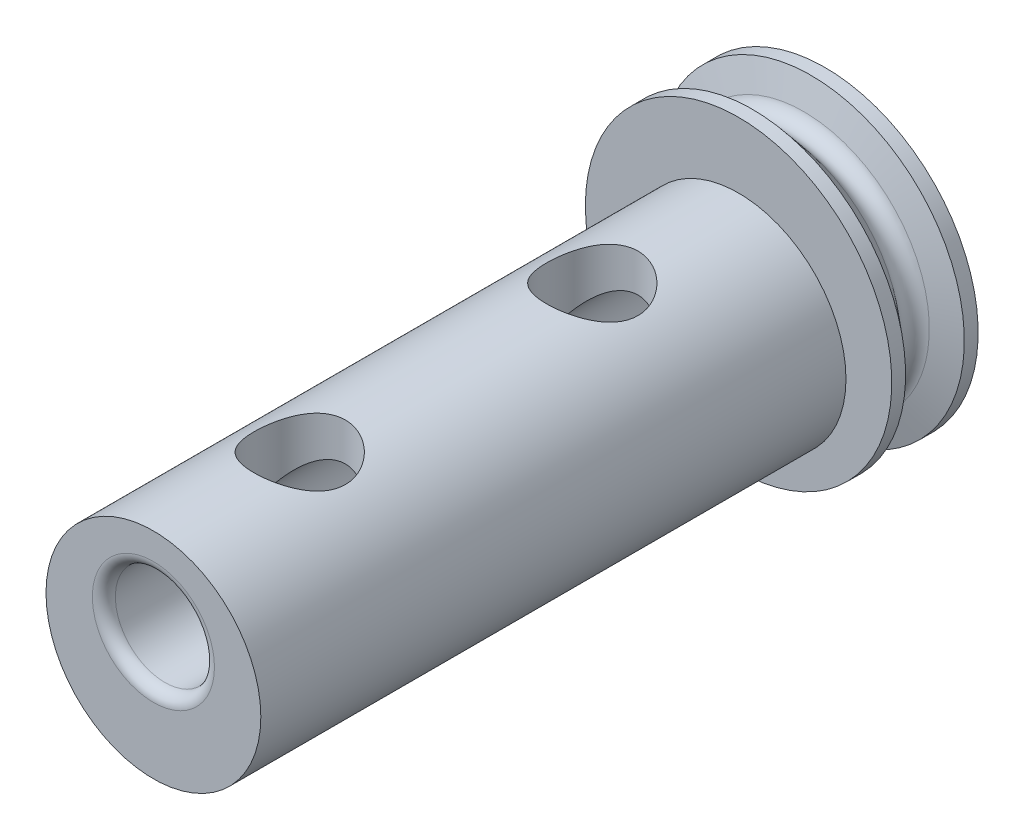
SolidWorks part; units mm, degrees
ref_plane "Front Plane" through (0, 0, 0) normal (0, 0, 1) x (1, 0, 0)
ref_plane "Top Plane" through (0, 0, 0) normal (0, 1, 0) x (1, 0, 0)
ref_plane "Right Plane" through (0, 0, 0) normal (1, 0, 0) x (0, 0, -1)
sketch "Sketch1" plane through (0, 0, 0) normal (0, 0, 1) x (1, 0, 0)
  circle A0 centre (0, 1.72) radius 4.3
  circle A1 centre (0, 0) radius 9.525 construction
  circle A2 centre (0, 0) radius 9.525 construction
  circle A3 centre (0, 0) radius 9.325
  dimension "D1" = 8.6
  dimension "D3" = 0.2
  dimension "D2" = 1.72
extrude "Boss-Extrude1" add sketch "Sketch1" against normal up to surface (50.8 mm away)
sketch "Sketch2" plane through (0, 0, 0) normal (0, 1, 0) x (1, 0, 0)
  circle A0 centre (0, 38.1) radius 3.9688
  circle A1 centre (0, 12.7) radius 3.9688
  dimension "D1" = 7.9375
extrude "Cut-Extrude1" cut sketch "Sketch2" along normal blind 10.16 from offset 1.27
ref_axis "Axis1" through (0, 1.72, -50.8) along (0, 0, 1)
sketch "Sketch3" plane through (0, 0, 0) normal (1, 0, 0) x (0, 0, -1)
  line L0 (50.8, 6.02) -> (50.8, 15.02)
  line L1 (50.8, 15.02) -> (52, 15.02)
  line L2 (52, 15.02) -> (54.3954, 12.1652)
  line L3 (56.4576, 12.6224) -> (57.1, 15.02)
  line L4 (57.1, 15.02) -> (58.3, 15.02)
  line L5 (58.3, 15.02) -> (58.3, 6.02)
  line L6 (58.3, 6.02) -> (50.8, 6.02)
  arc A0 (54.3954, 12.1652) -> (56.4576, 12.6224) centre (55.3075, 12.9305) ccw
  dimension "D1" = 50
  dimension "D3" = 1.1906
  dimension "D2" = 1.2
  dimension "D4" = 9
  dimension "D5" = 75
  dimension "D6" = 7.5
revolve "Revolve1" add sketch "Sketch3" angle 360 about axis through (0, 1.72, -50.8) along (0, 0, 1)
fillet "Fillet1" radius 1 2 edges at (-4.3, 1.72, -58.3) (4.3, 1.72, 0)
